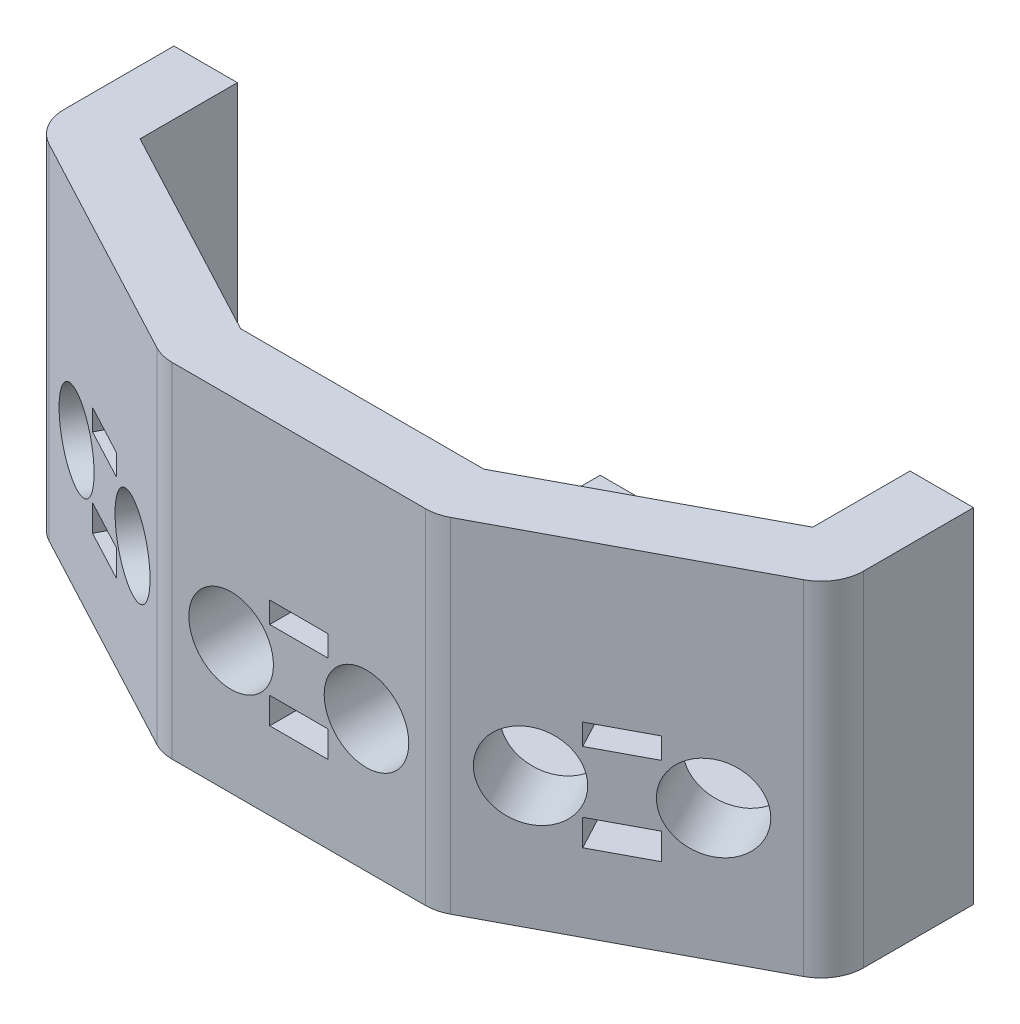
SolidWorks part; units mm, degrees
note: '?' marks a value the reader was unsure of.
ref_plane "前视基准面" through (0, 0, 0) normal (0, 0, 1) x (1, 0, 0)
ref_plane "上视基准面" through (0, 0, 0) normal (0, 1, 0) x (1, 0, 0)
ref_plane "右视基准面" through (0, 0, 0) normal (1, 0, 0) x (0, 0, -1)
sketch "Sketch1" plane through (0, 0, 0) normal (0, 1, 0) x (1, 0, 0)
  line L1 (0, 0) -> (40, 0)
  line L2 (0, 0) -> (0, 25)
  line L3 (0, 25) -> (40, 25)
  line L4 (40, 0) -> (40, 25)
  dimension "D1" = 40
  dimension "D2" = 25
extrude "Boss-Extrude1" add sketch "Sketch1" along normal blind 10
sketch "Sketch2" plane through (0, 10, 0) normal (0, 1, 0) x (1, 0, 0)
  line L0 (20, 0) -> (20, -40) construction
  line L1 (0, 0) -> (40, 0) construction
  line L2 (43, -40) -> (-3, -40)
  line L3 (-3, -40) -> (-43.6156, -18.4043)
  line L4 (20, -40) -> (20, -1040) construction
  line L5 (43, -40) -> (83.6156, -18.4043)
  line L6 (20, -40) -> (-247.9492, -1040) construction
  line L7 (-23.3078, -29.2022) -> (-492.7794, -912.1497) construction
  line L8 (-23.3078, -29.2022) -> (-256.1943, -1037.9443) construction
  line L9 (20, -1040) -> (-247.9492, -1040) construction
  line L10 (-492.7794, -912.1497) -> (-256.1943, -1037.9443) construction
  line L11 (0, 0) -> (-43.6156, 0)
  line L12 (-43.6156, 0) -> (-43.6156, -18.4043)
  line L13 (40, 0) -> (83.6156, 0)
  line L14 (83.6156, 0) -> (83.6156, -18.4043)
  line L15 (0, 0) -> (40, 0)
  point P6 (20, -40)
  dimension "D1" = 46
  dimension "D2" = 46
  dimension "D3" = 152
  dimension "D4" = 40
  dimension "D5" = 1000
  dimension "D6" = 15
  dimension "D7" = 1000
  dimension "D8" = 15
extrude "Boss-Extrude2" add sketch "Sketch2" against normal blind 10
sketch "Sketch3" plane through (0, 10, 0) normal (0, 1, 0) x (1, 0, 0)
  line L0 (-43.6156, -18.4043) -> (-3, -40)
  line L1 (-3, -40) -> (43, -40)
  line L2 (43, -40) -> (83.6156, -18.4043)
  line L3 (83.6156, -18.4043) -> (83.6156, 0)
  line L4 (83.6156, -18.4043) -> (83.6156, 0) construction
  line L5 (-43.6156, -18.4043) -> (-43.6156, 0)
  line L6 (-43.6156, 0) -> (-43.6156, -18.4043) construction
  dimension "D1" = 0
  dimension "D2" = 0
extrude "Extrude-Thin1" add sketch "Sketch3" along normal blind 30 and the other way blind 10 thin
fillet "Fillet1" radius 8 4 edges at (95.6156, 20, 25.6146) (-55.6156, 20, 25.6146) (45.9919, 20, 52) (-5.9919, 20, 52)
sketch "Sketch4" plane through (0, 0, 40) normal (0, 0, -1) x (-1, 0, 0)
  line L0 (-43, 40) -> (3, 10) construction
  line L1 (-32.8, 25) -> (-7.2, 25)
  line L2 (-20, 25) -> (-20, 33.3) construction
  line L3 (-20, 25) -> (-20, 17.2) construction
  line L5 (-25.5, 14.7) -> (-14.5, 14.7)
  line L6 (-25.5, 14.7) -> (-25.5, 19.7)
  line L7 (-25.5, 19.7) -> (-14.5, 19.7)
  line L8 (-14.5, 14.7) -> (-14.5, 19.7)
  line L9 (-25.5, 14.7) -> (-14.5, 19.7) construction
  line L10 (-25.5, 19.7) -> (-14.5, 14.7) construction
  line L11 (-25.5, 35.3) -> (-14.5, 35.3)
  line L12 (-25.5, 35.3) -> (-25.5, 31.3)
  line L13 (-25.5, 31.3) -> (-14.5, 31.3)
  line L14 (-14.5, 35.3) -> (-14.5, 31.3)
  line L15 (-25.5, 35.3) -> (-14.5, 31.3) construction
  line L16 (-25.5, 31.3) -> (-14.5, 35.3) construction
  circle A0 centre (-32.8, 25) radius 8
  circle A1 centre (-7.2, 25) radius 8
  point P7 (-20, 25)
  dimension "D8" = 16
  dimension "D9" = 16
  dimension "D1" = 11
  dimension "D2" = 11
  dimension "D3" = 25.6
  dimension "D4" = 4
  dimension "D5" = 5
  dimension "D6" = 6.3
  dimension "D7" = 5.3
extrude "Cut-Extrude1" cut sketch "Sketch4" against normal blind 30
sketch "Sketch5" plane through (0, 40, 0) normal (0, 1, 0) x (1, 0, 0)
  line L0 (-23.3078, -29.2022) -> (20, 52.248) construction
  line L1 (-43.6156, -18.4043) -> (-3, -40) construction
  line L2 (20, -40) -> (20, 52.248) construction
  line L3 (-3, -40) -> (43, -40) construction
  line L4 (63.3078, -29.2022) -> (20, 52.248) construction
  line L5 (43, -40) -> (83.6156, -18.4043) construction
  point P1 (0, 0)
  point P5 (20, 33.3356)
  point P12 (0, 0)
ref_axis "Axis1" through (20, 40, -52.248) along (0, 1, 0)?
pattern_circular "CirPattern1" count 2 every 28 about axis through (20, 40, -52.248) along (0, 1, 0) of "Cut-Extrude1"
sketch "Sketch6" plane through (0, 40, 0) normal (0, 1, 0) x (1, 0, 0)
  line L12 (47.7531, -51.0636) -> (91.3714, -27.8713)
  line L13 (95.6156, -20.8078) -> (95.6156, 0)
  line L14 (95.6156, 0) -> (83.6156, 0)
  line L15 (83.6156, 0) -> (83.6156, -18.4043)
  line L16 (83.6156, -18.4043) -> (43, -40)
  line L17 (43, -40) -> (-3, -40)
  line L18 (-3, -40) -> (-43.6156, -18.4043)
  line L19 (-43.6156, -18.4043) -> (-43.6156, 0)
  line L20 (-43.6156, 0) -> (-55.6156, 0)
  line L21 (-55.6156, 0) -> (-55.6156, -20.8078)
  line L22 (-51.3714, -27.8713) -> (-7.7531, -51.0636)
  line L23 (-3.9973, -52) -> (43.9973, -52)
  line L24 (47.7531, -51.0636) -> (91.3714, -27.8713)
  line L25 (95.6156, -20.8078) -> (95.6156, 0)
  line L26 (95.6156, 0) -> (83.6156, 0)
  line L27 (83.6156, 0) -> (83.6156, -18.4043)
  line L28 (83.6156, -18.4043) -> (43, -40)
  line L29 (43, -40) -> (-3, -40)
  line L30 (-3, -40) -> (-43.6156, -18.4043)
  line L31 (-43.6156, -18.4043) -> (-43.6156, 0)
  line L32 (-43.6156, 0) -> (-55.6156, 0)
  line L33 (-55.6156, 0) -> (-55.6156, -20.8078)
  line L34 (-51.3714, -27.8713) -> (-7.7531, -51.0636)
  line L35 (-3.9973, -52) -> (43.9973, -52)
  arc A4 (91.3714, -27.8713) -> (95.6156, -20.8078) centre (87.6156, -20.8078) ccw
  arc A5 (-55.6156, -20.8078) -> (-51.3714, -27.8713) centre (-47.6156, -20.8078) ccw
  arc A6 (-7.7531, -51.0636) -> (-3.9973, -52) centre (-3.9973, -44) ccw
  arc A7 (43.9973, -52) -> (47.7531, -51.0636) centre (43.9973, -44) ccw
  arc A8 (91.3714, -27.8713) -> (95.6156, -20.8078) centre (87.6156, -20.8078) ccw
  arc A9 (-55.6156, -20.8078) -> (-51.3714, -27.8713) centre (-47.6156, -20.8078) ccw
  arc A10 (-7.7531, -51.0636) -> (-3.9973, -52) centre (-3.9973, -44) ccw
  arc A11 (43.9973, -52) -> (47.7531, -51.0636) centre (43.9973, -44) ccw
  dimension "D1" = 0
extrude "Boss-Extrude3" add sketch "Sketch6" along normal blind 25
sketch "Sketch7" plane through (0, 10, 0) normal (0, 1, 0) x (1, 0, 0)
  line L0 (0, 12.5) -> (40, 12.5) construction
  line L1 (0, 25) -> (0, 0) construction
  line L2 (40, 0) -> (40, 25) construction
  circle A0 centre (10, 12.5) radius 2
  circle A1 centre (30, 12.5) radius 2
  dimension "D1" = 10
  dimension "D2" = 10
  dimension "D3" = 4
  dimension "D4" = 4
extrude "Cut-Extrude2" cut sketch "Sketch7" against normal through all
